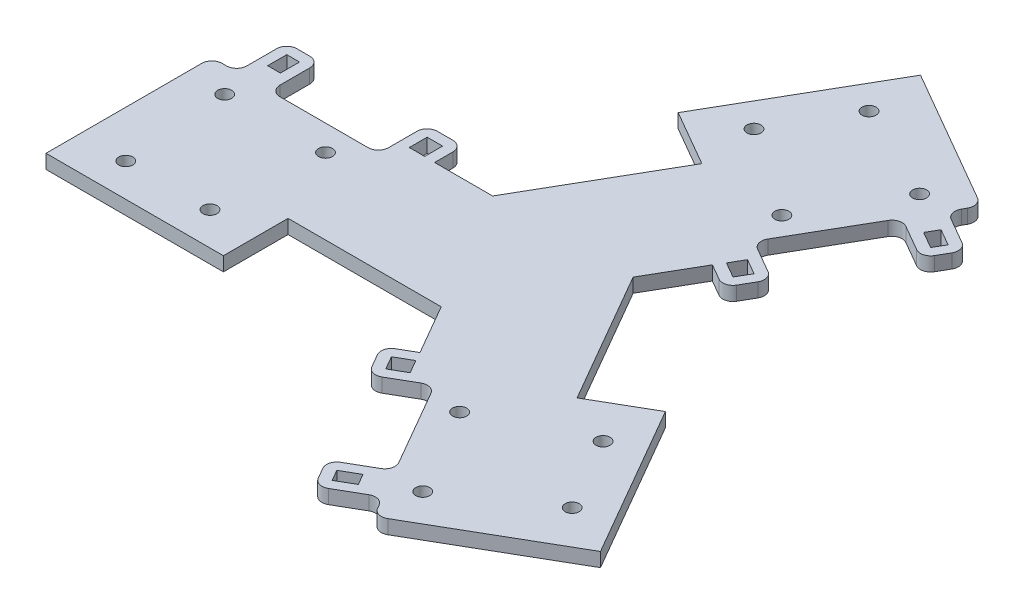
SolidWorks part; units mm, degrees
note: '?' marks a value the reader was unsure of.
material "Acrylic (Medium-high impact)"
ref_plane "Front Plane" through (0, 0, 0) normal (0, 0, 1) x (1, 0, 0)
ref_plane "Top Plane" through (0, 0, 0) normal (0, 1, 0) x (1, 0, 0)
ref_plane "Right Plane" through (0, 0, 0) normal (1, 0, 0) x (0, 0, -1)
sketch "Sketch3" plane through (0, 0, 0) normal (0, 1, 0) x (1, 0, 0)
  line L0 (26.2283, 11.4728) -> (26.2283, -47.5272) construction
  line L1 (-5.5217, 11.4728) -> (57.9783, 11.4728)
  line L2 (-5.5217, 11.4728) -> (-5.5217, -47.5272)
  line L3 (-5.5217, -47.5272) -> (57.9783, -47.5272)
  line L4 (57.9783, 11.4728) -> (57.9783, -47.5272)
  line L6 (-8.5217, -50.5272) -> (60.9783, -50.5272)
  line L7 (-8.5217, -50.5272) -> (-8.5217, 14.4728)
  line L8 (-8.5217, 14.4728) -> (60.9783, 14.4728)
  line L9 (60.9783, -50.5272) -> (60.9783, 14.4728)
  line L10 (-8.5217, -50.5272) -> (60.9783, 14.4728) construction
  line L11 (-8.5217, 14.4728) -> (60.9783, -50.5272) construction
  point P6 (26.2283, -18.0272)
  dimension "D1" = 63.5
  dimension "D2" = 59
  dimension "D3" = 3
  dimension "D4" = 3
extrude "Boss-Extrude1" add sketch "Sketch3" along normal blind 3
sketch "Sketch4" plane through (0, 3, 0) normal (0, 1, 0) x (1, 0, 0)
  line L1 (-8.5217, 14.4728) -> (60.9783, 14.4728)
  line L2 (-8.5217, 14.4728) -> (-8.5217, -50.5272)
  line L3 (-8.5217, -50.5272) -> (60.9783, -50.5272)
  line L4 (60.9783, 14.4728) -> (60.9783, -50.5272)
extrude "Boss-Extrude2" add sketch "Sketch4" along normal blind 5.5
ref_plane "Plane1" through (0, 0, -6.5828) normal (0, 0, 1) x (1, 0, 0)
sketch "Sketch5" plane through (0, 3, 0) normal (0, -1, 0) x (-1, 0, 0)
  line L0 (5.5217, 4.4787) -> (-57.9783, 4.4787) construction
  line L1 (-57.9783, -47.5272) -> (-57.9783, 11.4728) construction
  text T0 "Group 1\r\nJohns Hopkins " font "Constantia" height in points 15
ref_plane "Plane2" through (120.9783, 0, 0) normal (1, 0, 0) x (0, 0, -1)
ref_axis "Axis1" through (120.9783, 6.3, -6.5828) along (0, -1, 0)?
pattern_circular "CirPattern3" count 3 over 360 about axis through (120.9783, 0, -6.5828) along (0, 1, 0) of bodies 102 107
sketch "Sketch9" plane through (0, 3, 0) normal (0, -1, 0) x (1, 0, 0)
  line L0 (197.0887, 99.3844) -> (174.3754, 112.498) construction
  line L3 (195.0872, 95.9176) -> (201.4144, 106.8766) construction
  line L4 (174.3754, 112.498) -> (139.3633, 51.8553) construction
  line L5 (139.3633, 51.8553) -> (162.0767, 38.7417) construction
  line L6 (197.0887, 99.3844) -> (174.3754, 112.498)
  line L7 (174.3754, 112.498) -> (139.3633, 51.8553)
  line L8 (139.3633, 51.8553) -> (162.0767, 38.7417)
  line L9 (162.0767, 38.7417) -> (197.0887, 99.3844)
extrude "Cut-Extrude2" cut sketch "Sketch9" along normal blind 10
sketch "Sketch10" plane through (0, 3, 0) normal (0, -1, 0) x (1, 0, 0)
  line L0 (196.926, 99.1025) -> (162.176, 38.9137)
  line L1 (162.176, 38.9137) -> (159.5779, 40.4137)
  line L2 (144.1453, 49.3237) -> (162.176, 38.9137) construction
  line L3 (159.5779, 40.4137) -> (194.3279, 100.6025)
  line L4 (196.926, 99.1025) -> (178.8953, 109.5125) construction
  line L5 (194.3279, 100.6025) -> (196.926, 99.1025)
  dimension "D1" = 3
extrude "Boss-Extrude3" add sketch "Sketch10" along a picked direction on the side of the normal blind 3
sketch "Sketch11" plane through (0, 3, 0) normal (0, -1, 0) x (1, 0, 0)
  line L0 (166.0961, -110.5891) -> (25166.0961, -43411.8593) construction
  line L2 (174.6198, -125.3528) -> (139.7, -64.8699)
  line L3 (139.7, -64.8699) -> (160.0489, -53.1215)
  line L4 (160.0489, -53.1215) -> (194.9687, -113.6043)
  line L5 (194.9687, -113.6043) -> (174.6198, -125.3528)
extrude "Cut-Extrude3" cut sketch "Sketch11" along normal blind 10
sketch "Sketch12" plane through (0, 3, 0) normal (0, -1, 0) x (-1, 0, 0)
  line L0 (-174.5306, 125.1981) -> (-139.7806, 65.0094)
  line L1 (-173.0306, 122.6) -> (-174.5306, 125.1981) construction
  line L2 (-139.7806, 65.0094) -> (-141.2806, 67.6074) construction
  line L3 (-139.7806, 65.0094) -> (-142.3786, 63.5094)
  line L4 (-139.7806, 65.0094) -> (-157.8112, 54.5994) construction
  line L5 (-142.3786, 63.5094) -> (-177.1286, 123.6981)
  line L6 (-192.5612, 114.7881) -> (-174.5306, 125.1981) construction
  line L7 (-177.1286, 123.6981) -> (-174.5306, 125.1981)
  dimension "D1" = 3
extrude "Boss-Extrude4" add sketch "Sketch12" along normal blind 3
sketch "Sketch13" plane through (0, 3, 0) normal (0, -1, 0) x (-1, 0, 0)
  line L0 (-60.9783, -50.5272) -> (-60.9783, 14.4728) construction
  line L1 (-60.9783, -3.3472) -> (22.0005, -3.3472)
  line L2 (-60.9783, -3.3472) -> (-60.9783, 53.6934)
  line L3 (-60.9783, 53.6934) -> (22.0005, 53.6934)
  line L4 (22.0005, -3.3472) -> (22.0005, 53.6934)
  line L5 (8.5217, -50.5272) -> (-60.9783, -50.5272) construction
  dimension "D1" = 47.18
extrude "Cut-Extrude4" cut sketch "Sketch13" along normal blind 3
sketch "Sketch15" plane through (0, 3, 0) normal (0, -1, 0) x (1, 0, 0)
  line L0 (-8.5217, 3.3472) -> (-8.5217, 50.5272) construction
  line L1 (60.9783, 3.3472) -> (-8.5217, 3.3472)
  line L2 (60.9783, 3.3472) -> (60.9783, 6.3472)
  line L3 (60.9783, 6.3472) -> (-8.5217, 6.3472)
  line L4 (-8.5217, 3.3472) -> (-8.5217, 6.3472)
  dimension "D1" = 3
extrude "Boss-Extrude5" add sketch "Sketch15" along normal blind 3
sketch "Sketch16" plane through (0, 3, 0) normal (0, -1, 0) x (1, 0, 0)
  line L0 (60.9783, -14.4728) -> (-8.5217, -14.4728) construction
  line L1 (1.1783, -14.4728) -> (14.1783, -14.4728)
  line L2 (1.1783, -14.4728) -> (1.1783, -34.0928)
  line L3 (1.1783, -34.0928) -> (14.1783, -34.0928)
  line L4 (14.1783, -14.4728) -> (14.1783, -34.0928)
  line L5 (5.1783, -22.5928) -> (5.1783, -25.5928) construction
  line L6 (10.1783, -30.0928) -> (10.1783, -27.0928) construction
  line L7 (5.1783, -30.0928) -> (10.1783, -30.0928) construction
  line L8 (10.1783, -25.5928) -> (10.1783, -22.5928) construction
  line L13 (5.1783, -22.5928) -> (10.1783, -22.5928)
  line L14 (5.1783, -22.5928) -> (5.1783, -30.0928)
  line L15 (5.1783, -30.0928) -> (10.1783, -30.0928)
  line L16 (10.1783, -22.5928) -> (10.1783, -30.0928)
  line L17 (10.1783, -22.5928) -> (5.1783, -22.5928) construction
  line L18 (111.8042, -22.4728) -> (60.9783, -22.4728) construction
  line L19 (56.6783, -14.4728) -> (60.9783, -14.4728)
  line L20 (56.6783, -14.4728) -> (56.6783, -33.5928)
  line L21 (56.6783, -33.5928) -> (70.7258, -33.5928)
  line L22 (70.7258, -22.4728) -> (70.7258, -33.5928)
  line L25 (70.7258, -22.4728) -> (60.9783, -22.4728)
  line L26 (60.9783, -14.4728) -> (60.9783, -22.4728)
  line L28 (66.7258, -29.5928) -> (60.6783, -29.5928) construction
  line L29 (60.6783, -22.5928) -> (60.6783, -25.0928) construction
  line L30 (60.6783, -22.5928) -> (66.7258, -22.5928)
  line L31 (60.6783, -22.5928) -> (60.6783, -29.5928)
  line L32 (60.6783, -29.5928) -> (66.7258, -29.5928)
  line L33 (66.7258, -22.5928) -> (66.7258, -29.5928)
  line L34 (66.7258, -29.5928) -> (66.7258, -22.5928) construction
  line L35 (60.6783, -22.5928) -> (66.7258, -22.5928) construction
  dimension "D1" = 4
  dimension "D2" = 4
  dimension "D3" = 4
  dimension "D4" = 4
  dimension "D5" = 4
  dimension "D6" = 4
extrude "Boss-Extrude6" add sketch "Sketch16" against normal blind 5.5
pattern_circular "CirPattern6" count 3 over 360 about axis through (120.9783, 0, -6.5828) along (0, 1, 0) of bodies 117 118
fillet "Fillet1" radius 4 4 edges at (70.7258, 5.75, -33.5928) (56.6783, 5.75, -33.5928) (14.1783, 5.75, -34.0928) (1.1783, 5.75, -34.0928)
fillet "Fillet2" radius 4 4 edges at (169.4959, 5.75, -36.5978) (176.5196, 5.75, -48.7633) (198.2026, 5.75, -85.3193) (204.7026, 5.75, -96.5777)
fillet "Fillet3" radius 4 4 edges at (122.7132, 5.75, 50.4421) (129.7369, 5.75, 62.6076) (150.5539, 5.75, 99.6637) (157.0539, 5.75, 110.922)
fillet "Fillet4" radius 4 4 edges at (187.7112, 5.75, -106.3877) (181.2112, 5.75, -95.1293) (159.9612, 5.75, -58.3233) (192.5612, 5.75, -114.7881)
fillet "Fillet5" radius 4 3 edges at (167.5453, 5.75, 89.8537) (146.2953, 5.75, 53.0476) (178.8953, 5.75, 109.5125)
fillet "Fillet6" radius 4 4 edges at (1.1783, 5.75, -14.4728) (14.1783, 5.75, -14.4728) (56.6783, 5.75, -14.4728) (-8.5217, 5.75, -14.4728)
fillet "Fillet7" radius 4 1 edges at (192.5612, 5.75, -114.7881)
fillet "Fillet8" radius 4 1 edges at (174.0453, 5.75, 101.112)
fillet "Fillet9" radius 4 1 edges at (178.8953, 5.75, 109.5125)
sketch "Sketch17" plane through (0, 3, 0) normal (0, -1, 0) x (-1, 0, 0)
  circle A0 centre (-121.9029, 96.4043) radius 2.75
  circle A1 centre (-138.4029, 124.9832) radius 2.75
  dimension "D1" = 5.5
  dimension "D2" = 5.5
extrude "Cut-Extrude5" cut sketch "Sketch17" against normal blind 10
sketch "Sketch18" plane through (0, 3, 0) normal (0, -1, 0) x (1, 0, 0)
  line L0 (149.1441, -59.5874) -> (183.9009, -119.7881) construction
  line L1 (164.7394, -50.5994) -> (142.3786, -63.5094) construction
  line L2 (189.0971, -116.7881) -> (177.1286, -123.6981) construction
  line L4 (157.8112, -54.5994) -> (190.5612, -111.324) construction
  line L5 (161.9612, -61.7874) -> (179.2112, -91.6652) construction
  circle A0 centre (176.4009, -106.7977) radius 2.75
  circle A1 centre (156.6509, -72.5897) radius 2.75
  dimension "D1" = 5.5
  dimension "D2" = 5.5
  dimension "D3" = 15
  dimension "D4" = 15
  dimension "D5" = 10
extrude "Cut-Extrude6" cut sketch "Sketch18" against normal blind 10
sketch "Sketch20" plane through (0, 0, 0) normal (0, -1, 0) x (1, 0, 0)
  line L0 (-5.5217, 47.5272) -> (57.9783, 47.5272) construction
  line L1 (58.7783, 48.3272) -> (-6.3217, 48.3272)
  line L2 (58.7783, 48.3272) -> (58.7783, 5.5472)
  line L3 (58.7783, 5.5472) -> (-6.3217, 5.5472)
  line L4 (-6.3217, 48.3272) -> (-6.3217, 5.5472)
  line L5 (57.9783, 47.5272) -> (57.9783, 6.3472) construction
  line L6 (57.9783, 6.3472) -> (-5.5217, 6.3472) construction
  line L7 (-5.5217, 6.3472) -> (-5.5217, 47.5272) construction
  line L16 (195.1331, 97.5972) -> (162.5831, 41.219)
  line L17 (162.5831, 41.219) -> (199.6317, 19.829)
  line L18 (199.6317, 19.829) -> (232.1817, 76.2072)
  line L19 (232.1817, 76.2072) -> (195.1331, 97.5972)
  line L20 (195.1331, 97.5972) -> (162.5831, 41.219)
  line L21 (162.5831, 41.219) -> (199.6317, 19.829)
  line L22 (199.6317, 19.829) -> (232.1817, 76.2072)
  line L23 (232.1817, 76.2072) -> (195.1331, 97.5972)
  line L28 (174.1234, -122.8929) -> (141.5734, -66.5146)
  line L29 (141.5734, -66.5146) -> (104.5248, -87.9046)
  line L30 (104.5248, -87.9046) -> (137.0748, -144.2829)
  line L31 (137.0748, -144.2829) -> (174.1234, -122.8929)
  line L32 (174.1234, -122.8929) -> (141.5734, -66.5146)
  line L33 (141.5734, -66.5146) -> (104.5248, -87.9046)
  line L34 (104.5248, -87.9046) -> (137.0748, -144.2829)
  line L35 (137.0748, -144.2829) -> (174.1234, -122.8929)
  dimension "D1" = 0.8
  dimension "D2" = 0.8
  dimension "D3" = 0.8
  dimension "D4" = 0.8
  dimension "D5" = 0.8
  dimension "D6" = 0.8
extrude "Cut-Extrude7" cut sketch "Sketch20" against normal blind 3
pattern_circular "CirPattern7" count 3 over 360 about axis through (120.9783, 0, -6.5828) along (0, 1, 0) of "Cut-Extrude6", "Cut-Extrude5"
sketch "Sketch23" plane through (0, 8.5, 0) normal (0, 1, 0) x (1, 0, 0)
  line L0 (120.9783, 6.5828) -> (60.9783, 6.5828) construction
  line L1 (60.9783, -50.5272) -> (60.9783, 22.4728) construction
sketch "Sketch27" plane through (0, 3, 0) normal (0, -1, 0) x (1, 0, 0)
  line L1 (-84.0055, 118.3417) -> (335.8093, 118.3417)
  line L2 (-84.0055, 118.3417) -> (-84.0055, -209.4657)
  line L3 (-84.0055, -209.4657) -> (335.8093, -209.4657)
  line L4 (335.8093, 118.3417) -> (335.8093, -209.4657)
extrude "Cut-Extrude9" cut sketch "Sketch27" along normal blind 390 contours L1 L4 L3 L2
sketch "Sketch28" plane through (0, 3, 0) normal (0, -1, 0) x (1, 0, 0)
  line L0 (60.9783, 25.1971) -> (60.9783, -22.4728)
  line L1 (137.2172, 53.3237) -> (200.437, 16.8237) construction
  line L2 (82.2041, 53.3237) -> (82.4441, 53.3237)
  line L3 (164.7394, -50.5994) -> (101.5196, -87.0994) construction
  line L4 (60.9783, -22.4728) -> (148.5005, -22.4728)
  line L5 (137.2172, 53.3237) -> (93.456, -22.4728)
  line L6 (164.7394, -50.5994) -> (120.9783, 25.1971)
  line L7 (93.456, -22.4728) -> (123.456, -74.4343)
  line L8 (132.3434, 44.8821) -> (137.2172, 53.3237) construction
  line L10 (178.5005, 29.4887) -> (137.2172, 53.3237)
  line L11 (123.456, -74.4343) -> (164.7394, -50.5994)
  line L14 (120.9783, 25.1971) -> (60.9783, 25.1971)
  line L15 (60.9783, -22.4728) -> (60.9783, 50.5272) construction
  line L16 (148.5005, -22.4728) -> (178.5005, 29.4887)
  dimension "D1" = 60
extrude "Boss-Extrude7" add sketch "Sketch28" against normal up to surface (5.5 mm away) contours L4 L6 L5 | L5 L14 L0 L4 | L6 L16 L10 L5 | L7 L11 L6 L4 up to face at (48.3598, 8.5, -5.8478)
sketch "Sketch31" plane through (0, 3, 0) normal (0, -1, 0) x (-1, 0, 0)
  line L0 (-9.7283, -37.5272) -> (-42.7283, -37.5272) construction
  line L1 (-45.9783, 4.4728) -> (-6.4783, 4.4728) construction
  line L2 (-9.7283, -37.5272) -> (-9.7283, 4.4728) construction
  line L3 (-6.4783, 4.4728) -> (-6.4783, -37.5272) construction
  dimension "D1" = 42
  dimension "D2" = 3.25
